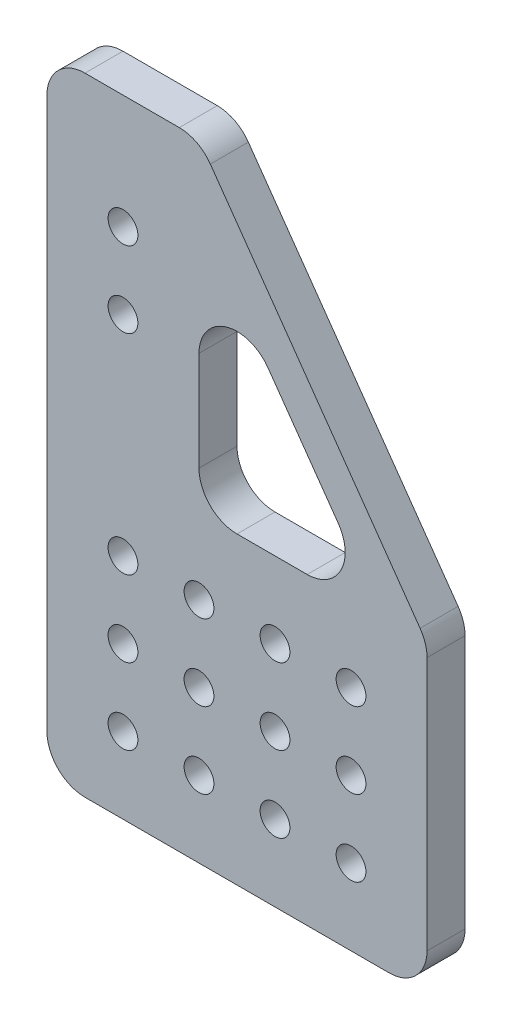
SolidWorks part; units mm, degrees
material "6061-T6 (SS)"
ref_plane "Front Plane" through (0, 0, 0) normal (0, 0, 1) x (1, 0, 0)
ref_plane "Top Plane" through (0, 0, 0) normal (0, 1, 0) x (1, 0, 0)
ref_plane "Right Plane" through (0, 0, 0) normal (1, 0, 0) x (0, 0, -1)
sketch "Sketch1" plane through (0, 0, 0) normal (0, 0, 1) x (1, 0, 0)
  line L0 (0, 0) -> (0, 104.775)
  line L1 (0, 104.775) -> (25.4, 104.775)
  line L2 (25.4, 104.775) -> (63.5, 50.8)
  line L3 (63.5, 50.8) -> (63.5, 0)
  line L4 (63.5, 0) -> (0, 0)
  circle A0 centre (12.7, 85.725) radius 2.4892
  circle A1 centre (12.7, 73.025) radius 2.4892
  circle A2 centre (12.7, 12.7) radius 2.4892
  dimension "D8" = 12.7
  dimension "D9" = 4.9784
  dimension "D1" = 104.775
  dimension "D2" = 25.4
  dimension "D3" = 63.5
  dimension "D4" = 50.8
  dimension "D5" = 12.7
  dimension "D6" = 12.7
  dimension "D7" = 19.05
extrude "Boss-Extrude1" add sketch "Sketch1" along normal mid plane 6.35
pattern_linear "LPattern1" count 4 spacing 12.7 along (1, 0, 0) count 3 spacing 12.7 along (0, 1, 0) of face at (15.1892, 12.7, 3.175)
sketch "Sketch2" plane through (0, 0, 3.175) normal (0, 0, 1) x (1, 0, 0)
  line L1 (25.4, 93.7638) -> (25.4, 50.8)
  line L2 (0, 104.775) -> (0, 0) construction
  line L3 (55.7274, 50.8) -> (25.4, 93.7638)
  line L4 (25.4, 50.8) -> (55.7274, 50.8)
  line L5 (0, 0) -> (63.5, 0) construction
  line L6 (63.5, 50.8) -> (25.4, 104.775) construction
  dimension "D1" = 25.4
  dimension "D2" = 50.8
  dimension "D3" = 6.35
extrude "Cut-Extrude1" cut sketch "Sketch2" against normal through all
fillet "Fillet1" radius 6.35 8 edges at (0, 0, 0) (25.4, 104.775, 0) (63.5, 50.8, 0) (63.5, 0, 0) (0, 104.775, 0) (25.4, 93.7638, 0) (55.7274, 50.8, 0) (25.4, 50.8, 0)
